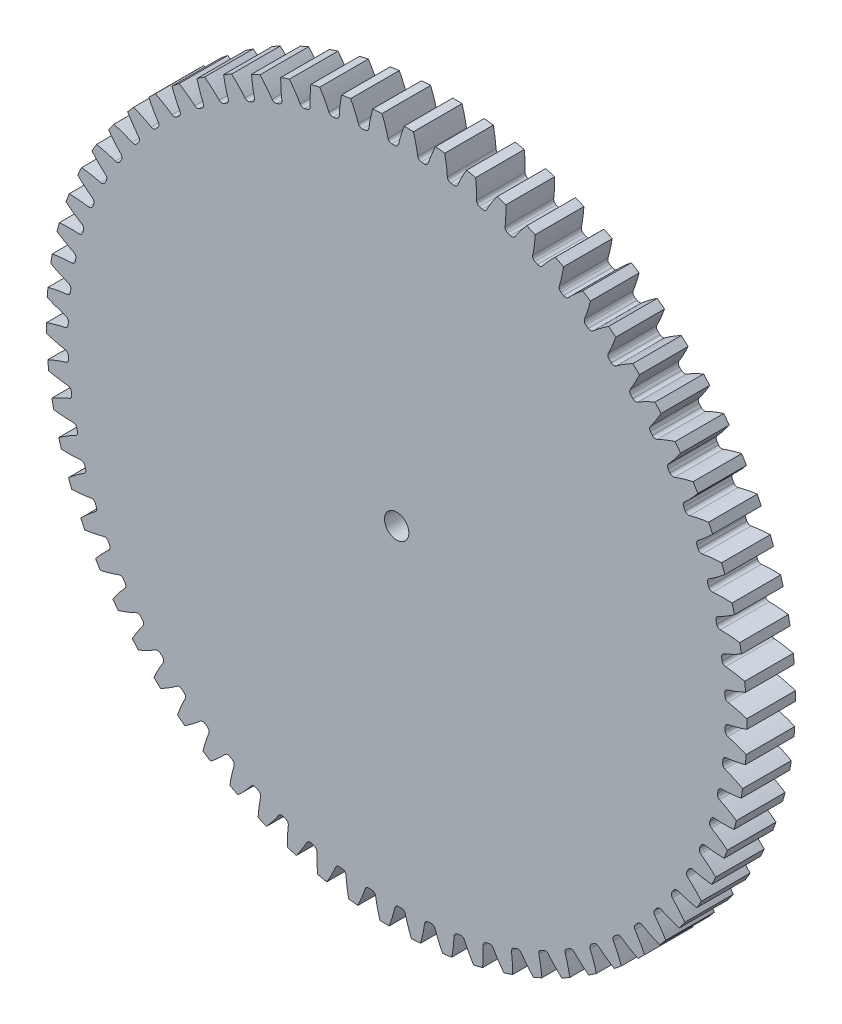
SolidWorks part; units mm, degrees
ref_plane "Front" through (0, 0, 0) normal (0, 0, 1) x (1, 0, 0)
ref_plane "Top" through (0, 0, 0) normal (0, 1, 0) x (1, 0, 0)
ref_plane "Right" through (0, 0, 0) normal (1, 0, 0) x (0, 0, -1)
sketch "Sketch3" plane through (0, 0, 0) normal (0, 0, 1) x (1, 0, 0)
  circle A0 centre (0, 0) radius 91.44
  dimension "od" = 182.88
extrude "gearBody" add sketch "Sketch3" along normal blind 12.7
sketch "Sketch2" plane through (0, 0, 0) normal (0, 0, 1) x (1, 0, 0)
  line L0 (0, 0) -> (79.5168, 32.9369) construction
  line L1 (107.4938, -20.5504) -> (0, 0) construction
  line L2 (0, 0) -> (36.3143, 0) construction
  line L3 (88.8936, -1.0687) -> (88.7543, -5.087) construction
  line L5 (88.824, -3.0778) -> (0, 0) construction
  line L7 (0, 0) -> (86.0683, 0) construction
  arc A0 (86.051, -1.7273) -> (85.9642, -4.2332) centre (0, 0) ccw construction
  arc A1 (91.4396, -0.2618) -> (91.2384, -6.0682) centre (0, 0) ccw construction
  arc A2 (88.8936, -1.0687) -> (88.7543, -5.087) centre (0, 0) ccw construction
  arc A3 (85.7353, -3.3621) -> (85.7624, -2.5804) centre (0, 0) ccw
  arc A4 (107.4938, -20.5504) -> (86.4707, -4.3696) centre (77.0462, -38.362) ccw
  arc A5 (107.4938, -20.5504) -> (108.6584, 13.0606) centre (0, 0) ccw
  arc A6 (108.6584, 13.0606) -> (86.5658, -1.6263) centre (79.5168, 32.9369) cw
  arc A7 (85.7624, -2.5804) -> (86.5658, -1.6263) centre (86.7665, -2.6106) cw
  arc A8 (86.4707, -4.3696) -> (85.7353, -3.3621) centre (86.7391, -3.4015) cw
  point P6 (108.6584, 13.0606)
  point P22 (107.4938, -20.5504)
  dimension "baseDia" = 172.1367
  dimension "od" = 182.88
  dimension "pd" = 177.8
  dimension "rd" = 171.6024
  dimension "rFillet" = 1.0046
  dimension "pointX" = 108.6584
  dimension "pointY" = 13.0606
  dimension "CTT" = 4.0183
  dimension "flankCenterAngle" = 22.5
extrude "toothCut" cut sketch "Sketch2" along normal through all
pattern_circular "CirPattern1" count 70 over 360 about axis through (0, 0, 12.7) along (0, 0, -1) of "toothCut"
ref_axis "toothSpace" through (0, 0, 0) along (0.9994, -0.0346, 0)
ref_axis "Axis2" through (91.1511, -7.2634, 0) along (-0.9968, 0.0794, 0)
sketch "hub1Dia" plane through (0, 0, 0) normal (0, 0, -1) x (-1, 0, 0)
  circle A0 centre (0, 0) radius 12.7
  dimension "hub1Dia" = 25.4
sketch "hub2Dia" plane through (0, 0, 12.7) normal (0, 0, 1) x (1, 0, 0)
  circle A0 centre (0, 0) radius 12.7
  dimension "hub2dia" = 25.4
sketch "boreDia" plane through (0, 0, 0) normal (0, 0, 1) x (1, 0, 0)
  circle A0 centre (0, 0) radius 3.175
  dimension "boreDia" = 6.35
extrude "bore" cut sketch "boreDia" against normal mid plane 25400
sketch "kwy1sketch" plane through (0, 0, 0) normal (0, 0, 1) x (1, 0, 0)
  line L0 (-5.3306, 0.3446) -> (0, 0) construction
  line L1 (29.3348, 10.8301) -> (27.6962, -14.517)
  line L2 (27.6962, -14.517) -> (-3.9877, -12.4687)
  line L3 (29.3348, 10.8301) -> (-2.3491, 12.8784)
  line L4 (-3.9877, -12.4687) -> (0, 0)
  line L5 (0, 0) -> (-2.3491, 12.8784)
  line L6 (0, 0) -> (85.7497, -2.9713) construction
  line L7 (28.5155, -1.8434) -> (0, 0) construction
  arc A7 (85.7353, -3.3621) -> (85.7624, -2.5804) centre (0, 0) ccw construction
  point P9 (28.5155, -1.8434)
  point P13 (-0.8892, 0.0575)
  dimension "kwy1width" = 25.4
  dimension "kwy1depth" = 28.575
  dimension "kwy1angle" = 1.714
  dimension "kwy1Depth2" = 31.75
sketch "kwy2sketch" plane through (0, 0, 0) normal (0, 0, 1) x (1, 0, 0)
  line L0 (85.7497, -2.9713) -> (0, 0) construction
  line L1 (0, 0) -> (-2.7731, -2.4363) construction
  line L2 (13.0848, 28.4009) -> (29.8492, 9.3191)
  line L3 (29.8492, 9.3191) -> (5.997, -11.6364)
  line L4 (13.0848, 28.4009) -> (-10.7674, 7.4453)
  line L5 (5.997, -11.6364) -> (0, 0)
  line L6 (0, 0) -> (-10.7674, 7.4453)
  arc A2 (85.7353, -3.3621) -> (85.7624, -2.5804) centre (0, 0) ccw construction
  point P10 (21.467, 18.86)
  dimension "kwy2angle" = 43.286
  dimension "kwy2Width" = 25.4
  dimension "kwy2depth" = 28.575
  dimension "kwy2Depth2" = 31.75
sketch "kwy3sketch" plane through (0, 0, 0) normal (0, 0, 1) x (1, 0, 0)
  line L0 (85.7497, -2.9713) -> (0, 0) construction
  line L1 (0, 0) -> (-0.1723, -2.665) construction
  line L2 (-10.8301, 29.3348) -> (14.517, 27.6962)
  line L3 (14.517, 27.6962) -> (12.4687, -3.9877)
  line L4 (-10.8301, 29.3348) -> (-12.8784, -2.3491)
  line L5 (12.4687, -3.9877) -> (0, 0)
  line L6 (-12.8784, -2.3491) -> (0, 0)
  point P10 (1.8434, 28.5155)
  dimension "kwy3angle" = 88.286
  dimension "kwy3depth" = 28.575
  dimension "kwy3width" = 25.4
  dimension "kwy3Depth2" = 31.75
sketch "kwy4sketch" plane through (0, 0, 0) normal (0, 0, 1) x (1, 0, 0)
  line L0 (85.7497, -2.9713) -> (0, 0) construction
  line L1 (0, 0) -> (1.3782, -1.5687) construction
  line L2 (-9.3191, 29.8492) -> (-28.4009, 13.0848)
  line L3 (-28.4009, 13.0848) -> (-7.4453, -10.7674)
  line L4 (-7.4453, -10.7674) -> (0, 0)
  line L5 (11.6364, 5.997) -> (0, 0)
  line L6 (-9.3191, 29.8492) -> (11.6364, 5.997)
  point P15 (-18.86, 21.467)
  dimension "kwy4angle" = 133.286
  dimension "kwy4depth" = 28.575
  dimension "kwy4width" = 25.4
  dimension "kwy4Depth2" = 31.75
sketch "kwy5sketch" plane through (0, 0, 0) normal (0, 0, 1) x (1, 0, 0)
  line L0 (85.7497, -2.9713) -> (0, 0) construction
  line L1 (0, 0) -> (1.7896, -0.1157) construction
  line L2 (-27.6962, 14.517) -> (-29.3348, -10.8301)
  line L3 (-29.3348, -10.8301) -> (2.3491, -12.8784)
  line L4 (-27.6962, 14.517) -> (3.9877, 12.4687)
  line L5 (2.3491, -12.8784) -> (0, 0)
  line L6 (3.9877, 12.4687) -> (0, 0)
  point P10 (-28.5155, 1.8434)
  dimension "kwy5width" = 25.4
  dimension "kwy5depth" = 28.575
  dimension "kwy5angle" = 178.286
  dimension "kwy5Depth2" = 31.75
sketch "kwy6sketch" plane through (0, 0, 0) normal (0, 0, 1) x (1, 0, 0)
  line L0 (85.7497, -2.9713) -> (0, 0) construction
  line L1 (0, 0) -> (1.3462, 1.1827) construction
  line L2 (-29.8492, -9.3191) -> (-13.0848, -28.4009)
  line L3 (-13.0848, -28.4009) -> (10.7674, -7.4453)
  line L4 (-29.8492, -9.3191) -> (-5.997, 11.6364)
  line L5 (10.7674, -7.4453) -> (0, 0)
  line L6 (-5.997, 11.6364) -> (0, 0)
  point P10 (-21.467, -18.86)
  dimension "kwy6angle" = 223.286
  dimension "kwy6width" = 25.4
  dimension "kwy6depth" = 28.575
  dimension "kwy6Depth2" = 31.75
sketch "kwy7sketch" plane through (0, 0, 0) normal (0, 0, 1) x (1, 0, 0)
  line L0 (85.7497, -2.9713) -> (0, 0) construction
  line L1 (0, 0) -> (0.1295, 2.0033) construction
  line L2 (-14.517, -27.6962) -> (10.8301, -29.3348)
  line L3 (-14.517, -27.6962) -> (-12.4687, 3.9877)
  line L4 (10.8301, -29.3348) -> (12.8784, 2.3491)
  line L5 (-12.4687, 3.9877) -> (0, 0)
  line L6 (12.8784, 2.3491) -> (0, 0)
  point P10 (-1.8434, -28.5155)
  dimension "kwy7angle" = 88.286
  dimension "kwy7width" = 25.4
  dimension "kwy7depth" = 28.575
  dimension "kwy7angle1" = 268.286
  dimension "kwy7Depth2" = 31.75
sketch "kwy8sketch" plane through (0, 0, 0) normal (0, 0, 1) x (1, 0, 0)
  line L0 (85.7497, -2.9713) -> (0, 0) construction
  line L1 (0, 0) -> (-1.1772, 1.3399) construction
  line L2 (9.3191, -29.8492) -> (28.4009, -13.0848)
  line L3 (28.4009, -13.0848) -> (7.4453, 10.7674)
  line L4 (9.3191, -29.8492) -> (-11.6364, -5.997)
  line L5 (7.4453, 10.7674) -> (0, 0)
  line L6 (-11.6364, -5.997) -> (0, 0)
  point P10 (18.86, -21.467)
  dimension "kwy8angle" = 313.286
  dimension "kwy8width" = 25.4
  dimension "kwy8depth" = 28.575
  dimension "kwy8Depth2" = 31.75
sketch "centerLine" plane through (0, 0, 0) normal (0, 1, 0) x (1, 0, 0)
  line L0 (0, 36.4807) -> (0, -59.6309) construction
ref_plane "CB1plane" through (0, 0, 0) normal (0, 0, -1) x (-1, 0, 0)
sketch "CB1diameter" plane through (0, 0, 0) normal (0, 0, -1) x (-1, 0, 0)
  circle A0 centre (0, 0) radius 12.7
  dimension "CB1diameter" = 25.4
ref_plane "CB2plane" through (0, 0, 12.7) normal (0, 0, 1) x (1, 0, 0)
sketch "CB2diameter" plane through (0, 0, 12.7) normal (0, 0, 1) x (1, 0, 0)
  circle A0 centre (0, 0) radius 12.7
  dimension "CB2diameter" = 25.4
ref_axis "Axis1" through (0, 0, 50) along (0, 0, -1)
sketch3d "3DSketch1" plane through (0, 0, 0) normal (0, 0, 1) x (1, 0, 0)
